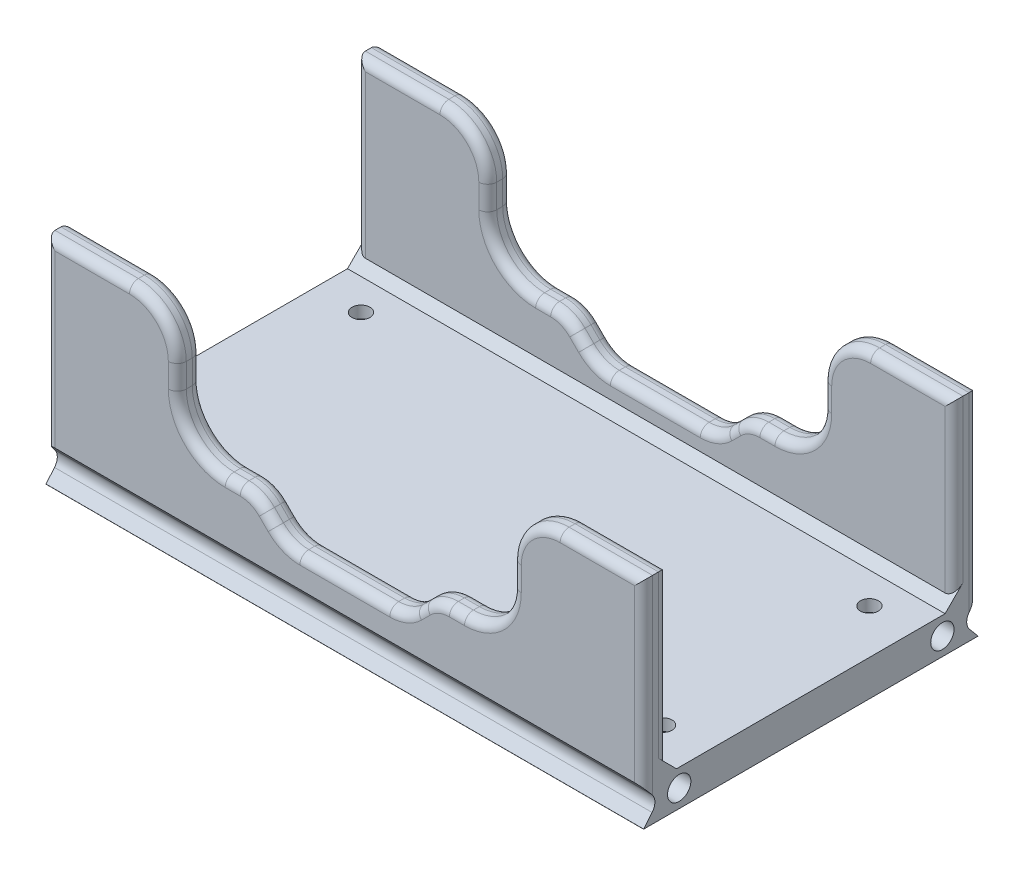
SolidWorks part; units mm, degrees
note: '?' marks a value the reader was unsure of.
ref_plane "Płaszczyzna przednia" through (0, 0, 0) normal (0, 0, 1) x (1, 0, 0)
ref_plane "Płaszczyzna górna" through (0, 0, 0) normal (0, 1, 0) x (1, 0, 0)
ref_plane "Płaszczyzna prawa" through (0, 0, 0) normal (1, 0, 0) x (0, 0, -1)
sketch "Szkic1" plane through (0, 0, 0) normal (0, 1, 0) x (1, 0, 0)
  line L1 (-49.95, -27.95) -> (49.95, -27.95)
  line L2 (-49.95, -27.95) -> (-49.95, 27.95)
  line L3 (-49.95, 27.95) -> (49.95, 27.95)
  line L4 (49.95, -27.95) -> (49.95, 27.95)
  line L5 (-49.95, -27.95) -> (49.95, 27.95) construction
  line L6 (-49.95, 27.95) -> (49.95, -27.95) construction
  point P0 (0, 0)
  dimension "D1" = 99.9
  dimension "D2" = 55.9
extrude "Dodanie-wyciągnięcie1" add sketch "Szkic1" along normal blind 6
sketch "Szkic2" plane through (0, 6, 0) normal (0, 1, 0) x (1, 0, 0)
  line L1 (-42.5, -17.25) -> (42.5, -17.25) construction
  line L2 (-42.5, -17.25) -> (-42.5, 17.25) construction
  line L3 (-42.5, 17.25) -> (42.5, 17.25) construction
  line L4 (42.5, -17.25) -> (42.5, 17.25) construction
  line L5 (-42.5, -17.25) -> (42.5, 17.25) construction
  line L6 (-42.5, 17.25) -> (42.5, -17.25) construction
  circle A0 centre (-42.5, 17.25) radius 1.5
  circle A1 centre (-42.5, -17.25) radius 1.5
  circle A2 centre (42.5, -17.25) radius 1.5
  circle A3 centre (42.5, 17.25) radius 1.5
  point P0 (0, 0)
  dimension "D1" = 3
  dimension "D2" = 3
  dimension "D3" = 3
  dimension "D4" = 3
  dimension "D5" = 85
  dimension "D6" = 34.5
extrude "Wytnij-wyciągnięcie1" cut sketch "Szkic2" against normal through all
sketch "Szkic3" plane through (0, 0, 0) normal (0, -1, 0) x (1, 0, 0)
  circle A0 centre (-42.5, 17.25) radius 3.5
  circle A1 centre (-42.5, -17.25) radius 3.5
  circle A2 centre (42.5, 17.25) radius 3.5
  circle A3 centre (42.5, -17.25) radius 3.5
  dimension "D1" = 7
  dimension "D2" = 7
  dimension "D3" = 7
  dimension "D4" = 7
extrude "Wytnij-wyciągnięcie2" cut sketch "Szkic3" against normal blind 4
sketch "Szkic5" plane through (-49.95, 0, 0) normal (-1, 0, 0) x (0, 0, 1)
  line L0 (-27.95, 0.0206) -> (-27.95, 5.9794)
  line L1 (-27.95, 6) -> (-27.95, 0) construction
  line L2 (-27.95, 5.9794) -> (-25.45, 3)
  line L3 (-25.45, 3) -> (-27.95, 0.0206)
  point P5 (-27.95, 3)
  point P7 (-27.95, 3)
  dimension "D1" = 40
  dimension "D2" = 40
  dimension "D3" = 2.5
extrude "Wytnij-wyciągnięcie6" cut sketch "Szkic5" against normal through all
fillet "Zaokrąglenie3" radius 2 1 edges at (0, 3, -25.45)
mirror "Lustro2" about plane through (0, 0, 0) normal (0, 0, 1) of "Zaokrąglenie3", "Wytnij-wyciągnięcie6"
sketch "Szkic6" plane through (-49.95, 0, 0) normal (-1, 0, 0) x (0, 0, 1)
  line L0 (0, 6) -> (0, 0) construction
  line L1 (-27.95, 6) -> (27.95, 6) construction
  circle A0 centre (0, 3) radius 2
  dimension "D1" = 4
extrude "Wytnij-wyciągnięcie3" cut sketch "Szkic6" against normal blind 1
fillet "Zaokrąglenie2" radius 2 1 edges at (-48.95, 3, 2)
sketch "Szkic9" plane through (0, 6, 0) normal (0, 1, 0) x (1, 0, 0)
  line L0 (-49.95, 27.95) -> (-49.95, -27.95) construction
  line L1 (49.95, 27.95) -> (-49.95, 27.95)
  line L2 (49.95, 27.95) -> (49.95, 23.95)
  line L3 (49.95, 23.95) -> (-49.95, 23.95)
  line L4 (-49.95, 27.95) -> (-49.95, 23.95)
  line L5 (49.95, 27.95) -> (-49.95, 23.95) construction
  line L6 (49.95, 23.95) -> (-49.95, 27.95) construction
  line L8 (49.95, -27.95) -> (-49.95, -27.95)
  line L9 (49.95, -27.95) -> (49.95, -23.95)
  line L10 (49.95, -23.95) -> (-49.95, -23.95)
  line L11 (-49.95, -27.95) -> (-49.95, -23.95)
  line L12 (49.95, -27.95) -> (-49.95, -23.95) construction
  line L13 (49.95, -23.95) -> (-49.95, -27.95) construction
  point P4 (0, 25.95)
  point P12 (0, -25.95)
  dimension "D1" = 4
  dimension "D2" = 4
extrude "Dodanie-wyciągnięcie2" add sketch "Szkic9" along normal blind 30
chamfer "Sfazowanie2" distance 1.5 angle 45 2 edges at (0, 6, 23.95) (0, 6, -23.95)
sketch "Szkic10" plane through (0, 0, 27.95) normal (0, 0, -1) x (-1, 0, 0)
  line L0 (-28, 16) -> (-28, 36)
  line L1 (-28, 16) -> (28, 16)
  line L2 (-28, 36) -> (28, 36)
  line L3 (28, 16) -> (28, 36)
  line L4 (-28, 16) -> (28, 36) construction
  line L5 (-28, 36) -> (28, 16) construction
  line L6 (-49.95, 36) -> (49.95, 36) construction
  point P1 (0, 26)
  dimension "D1" = 20
  dimension "D2" = 56
extrude "Wytnij-wyciągnięcie8" cut sketch "Szkic10" along normal up to next
ref_axis "Oś1" through (0, -1.3, 0) along (0, 1, 0)?
pattern_circular "Szyk kołowy1" count 2 every 180 about axis through (0, 16, 0) along (0, 0, 1) of "Wytnij-wyciągnięcie8"
fillet "Zaokrąglenie4" radius 8 8 edges at (-28, 16, 25.95) (28, 16, 25.95) (28, 36, 25.95) (-28, 36, 25.95) (-28, 16, -25.95) (-28, 36, -25.95) (28, 16, -25.95) (28, 36, -25.95)
sketch "Szkic11" plane through (0, 0, -27.95) normal (0, 0, -1) x (-1, 0, 0)
  line L0 (0, 0) -> (0, 11) construction
  line L1 (0, -1.3) -> (0, 27.3) construction
  line L2 (-10, 11) -> (10, 11)
  line L3 (10, 11) -> (15, 16)
  line L4 (20, 16) -> (-20, 16) construction
  line L5 (15, 16) -> (-15, 16)
  line L6 (-15, 16) -> (-10, 11)
  point P8 (0, 11)
  dimension "D1" = 135
  dimension "D2" = 135
  dimension "D3" = 30
  dimension "D4" = 5
extrude "Wytnij-wyciągnięcie9" cut sketch "Szkic11" against normal through all
fillet "Zaokrąglenie5" radius 6 8 edges at (10, 11, 25.95) (15, 16, 25.95) (-10, 11, 25.95) (-15, 16, 25.95) (-15, 16, -25.95) (-10, 11, -25.95) (15, 16, -25.95) (10, 11, -25.95)
chamfer "Sfazowanie3" distance 2 angle 45 4 edges at (42.5, 4, 13.75) (42.5, 4, -20.75) (-42.5, 4, 13.75) (-42.5, 4, -20.75)
sketch "Szkic7" plane through (49.95, 0, 0) normal (1, 0, 0) x (0, 0, -1)
  line L4 (-27.95, 0) -> (27.95, 0) construction
  line L12 (0, 19.8) -> (0, -19.8) construction
  circle A0 centre (-22, 3) radius 1.95
  circle A1 centre (22, 3) radius 1.95
  point P1 (-22, 3)
  dimension "D2" = 3.9
  dimension "D1" = 3
  dimension "D3" = 22
extrude "Wytnij-wyciągnięcie7" cut sketch "Szkic7" against normal blind 5.8
fillet "Zaokrąglenie6" radius 1.5 80 edges at (49.95, 21.75, -23.95) (-49.95, 21.75, -23.95) (42.975, 36, -27.95) (-42.975, 36, -23.95) (49.95, 21.75, 23.95) (-49.95, 21.75, 23.95) (42.975, 36, 23.95) (-42.975, 36, 27.95) (-28, 26, -27.95) (-28, 26, -23.95) (-18.7426, 16, -27.95) (18.7426, 16, -23.95) (-42.975, 36, -27.95) (28, 26, -27.95) (30.3431, 33.6569, -27.95) (-30.3431, 33.6569, -27.95) (28, 26, -23.95) (42.975, 36, -23.95) (30.3431, 33.6569, -23.95) (-30.3431, 33.6569, -23.95) (18.7426, 16, 27.95) (-18.7426, 16, 23.95) (-28, 26, 27.95) (-28, 26, 23.95) (28, 26, 27.95) (28, 26, 23.95) (42.975, 36, 27.95) (-30.3431, 33.6569, 27.95) (30.3431, 33.6569, 27.95) (-42.975, 36, 23.95) (-30.3431, 33.6569, 23.95) (30.3431, 33.6569, 23.95) (-25.6569, 18.3431, -27.95) (-25.6569, 18.3431, -23.95) (25.6569, 18.3431, -27.95) (25.6569, 18.3431, -23.95) (-25.6569, 18.3431, 27.95) (-25.6569, 18.3431, 23.95) (25.6569, 18.3431, 27.95) (25.6569, 18.3431, 23.95) (0, 11, 27.95) (0, 11, 23.95) (12.5, 13.5, 27.95) (12.5, 13.5, 23.95) (-12.5, 13.5, 23.95) (18.7426, 16, 23.95) (-15.1892, 15.5433, 23.95) (15.1892, 15.5433, 23.95) (-12.5, 13.5, 27.95) (-18.7426, 16, 27.95) (-15.1892, 15.5433, 27.95) (15.1892, 15.5433, 27.95) (-12.5, 13.5, -27.95) (-12.5, 13.5, -23.95) (0, 11, -23.95) (-18.7426, 16, -23.95) (12.5, 13.5, -23.95) (15.1892, 15.5433, -23.95) (-15.1892, 15.5433, -23.95) (0, 11, -27.95) (12.5, 13.5, -27.95) (18.7426, 16, -27.95) (15.1892, 15.5433, -27.95) (-15.1892, 15.5433, -27.95) (9.8108, 11.4567, 23.95) (9.8108, 11.4567, 27.95) (-9.8108, 11.4567, 23.95) (-9.8108, 11.4567, 27.95) (-9.8108, 11.4567, -27.95) (-9.8108, 11.4567, -23.95) (9.8108, 11.4567, -27.95) (9.8108, 11.4567, -23.95) (-49.95, 5.1325, -27.2394) (49.95, 5.1325, -27.2394) (49.95, 20.9897, 27.95) (-49.95, 20.9897, 27.95) (-49.95, 20.9897, -27.95) (49.95, 20.9897, -27.95) (-49.95, 5.1325, 27.2394) (49.95, 5.1325, 27.2394)
equation "\"M2.5_screw\"=3"
equation "\"D2@Szkic2\"=\"M2.5_screw\""
equation "\"M2.5_screw2\"=2.8"
equation "\"D1@Szkic2\"=\"M2.5_screw\""
equation "\"D3@Szkic2\"=\"M2.5_screw\""
equation "\"D4@Szkic2\"=\"M2.5_screw\""
equation "\"M2.5_screw_head\"=7"
equation "\"D1@Szkic3\"=\"M2.5_screw_head\""
equation "\"D2@Szkic3\"=\"M2.5_screw_head\""
equation "\"D3@Szkic3\"=\"M2.5_screw_head\""
equation "\"D4@Szkic3\"=\"M2.5_screw_head\""
